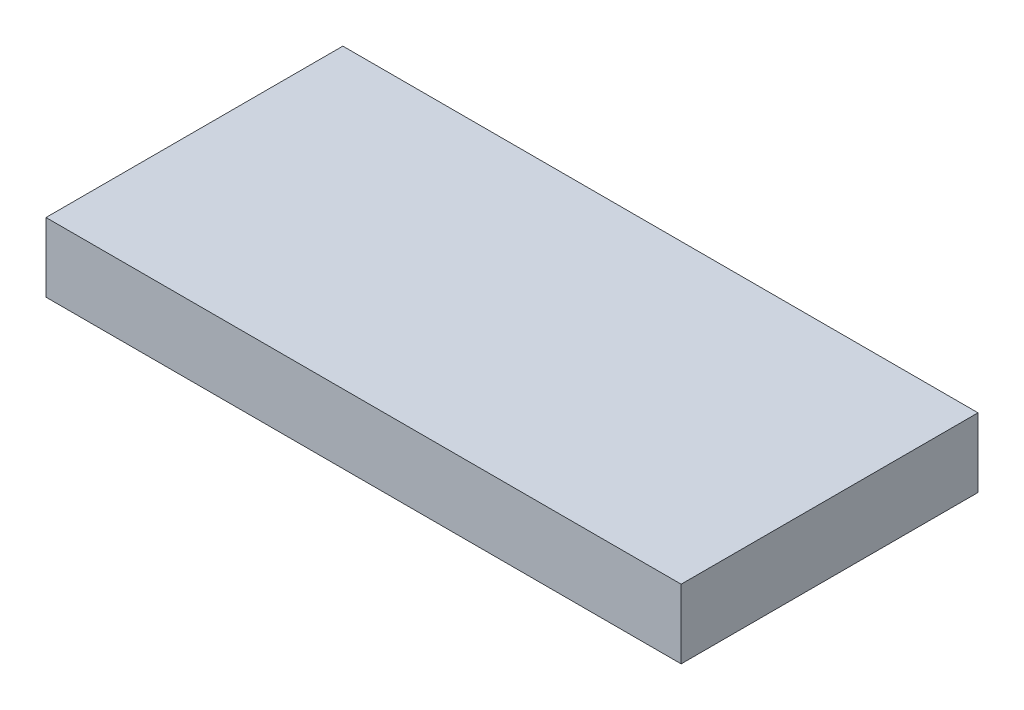
SolidWorks part; units mm, degrees
ref_plane "Front Plane" through (0, 0, 0) normal (0, 0, 1) x (1, 0, 0)
ref_plane "Top Plane" through (0, 0, 0) normal (0, 1, 0) x (1, 0, 0)
ref_plane "Right Plane" through (0, 0, 0) normal (1, 0, 0) x (0, 0, -1)
sketch "Sketch1" plane through (0, 0, 0) normal (0, 1, 0) x (1, 0, 0)
  line L1 (92, 43) -> (-92, 43)
  line L2 (92, 43) -> (92, -43)
  line L3 (92, -43) -> (-92, -43)
  line L4 (-92, 43) -> (-92, -43)
  line L5 (92, 43) -> (-92, -43) construction
  line L6 (92, -43) -> (-92, 43) construction
  point P0 (0, 0)
  dimension "D1" = 184
  dimension "D2" = 86
extrude "Boss-Extrude1" add sketch "Sketch1" along normal blind 20 contours L1 L4 L3 L2
sketch "Sketch2" plane through (0, 0, 0) normal (0, -1, 0) x (1, 0, 0)
  circle A0 centre (0, 0) radius 5.8
  dimension "D1" = 11.6
extrude "Cut-Extrude1" cut sketch "Sketch2" against normal blind 5.2
equation "\"D2@Sketch1\"=46+40"
equation "\"D1@Sketch1\"=144+40"
